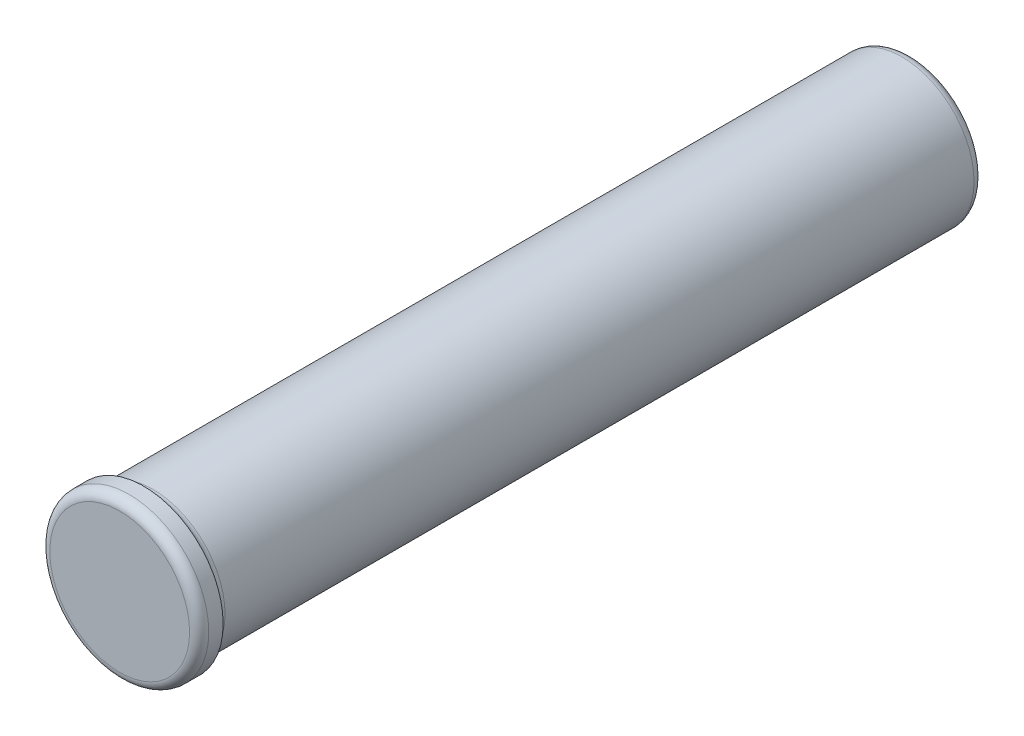
SolidWorks part; units mm, degrees
ref_plane "Front Plane" through (0, 0, 0) normal (0, 0, 1) x (1, 0, 0)
ref_plane "Top Plane" through (0, 0, 0) normal (0, 1, 0) x (1, 0, 0)
ref_plane "Right Plane" through (0, 0, 0) normal (1, 0, 0) x (0, 0, -1)
sketch "Sketch1" plane through (0, 0, 0) normal (0, 0, 1) x (1, 0, 0)
  circle A0 centre (0, 0) radius 0.15
  dimension "D1" = 0.3
extrude "Boss-Extrude1" add sketch "Sketch1" along normal blind 1.65
sketch "Sketch2" plane through (0, 0, 1.65) normal (0, 0, 1) x (1, 0, 0)
  circle A0 centre (0, 0) radius 0.1656
extrude "Boss-Extrude2" add sketch "Sketch2" against normal blind 0.05
fillet "Fillet1" radius 0.02 1 edges at (0.1656, 0, 1.65)
fillet "Fillet2" radius 0.02 1 edges at (0.15, 0, 1.6)
fillet "Fillet3" radius 0.02 1 edges at (0.15, 0, 0)
